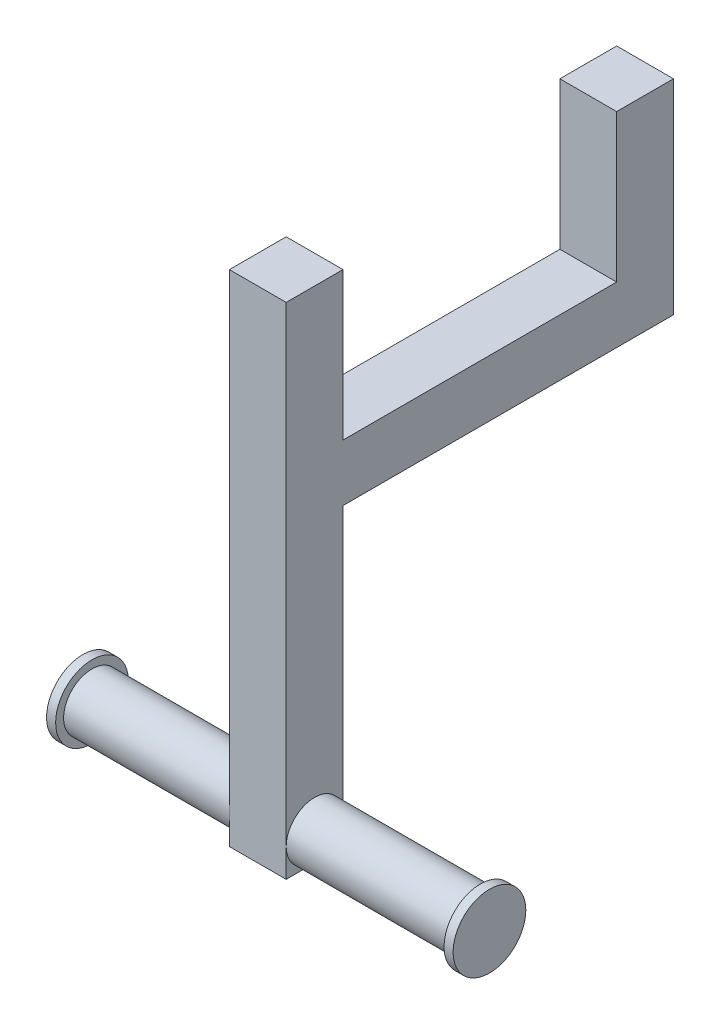
SolidWorks part; units mm, degrees
ref_plane "Front Plane" through (0, 0, 0) normal (0, 0, 1) x (1, 0, 0)
ref_plane "Top Plane" through (0, 0, 0) normal (0, 1, 0) x (1, 0, 0)
ref_plane "Right Plane" through (0, 0, 0) normal (1, 0, 0) x (0, 0, -1)
sketch "Sketch1" plane through (0, 0, 0) normal (0, 1, 0) x (1, 0, 0)
  line L0 (-60.0667, 70.9333) -> (-60.0667, -99.5667)
  line L1 (-85.0667, 70.9333) -> (-60.0667, 70.9333)
  line L2 (-85.0667, 70.9333) -> (-85.0667, -99.5667)
  line L3 (-85.0667, -99.5667) -> (-60.0667, -99.5667)
  line L5 (-85.0667, 70.9333) -> (-60.0667, 70.9333)
  line L6 (-85.0667, 70.9333) -> (-85.0667, 45.9333)
  line L7 (-85.0667, 45.9333) -> (-60.0667, 45.9333)
  line L8 (-60.0667, 70.9333) -> (-60.0667, 45.9333)
  line L9 (-85.0667, -99.5667) -> (-60.0667, -99.5667)
  line L10 (-85.0667, -99.5667) -> (-85.0667, -74.5667)
  line L11 (-85.0667, -74.5667) -> (-60.0667, -74.5667)
  line L12 (-60.0667, -99.5667) -> (-60.0667, -74.5667)
  dimension "D1" = 170.5
  dimension "D2" = 25
  dimension "D3" = 25
  dimension "D4" = 25
extrude "Boss-Extrude1" add sketch "Sketch1" along normal blind 25 contours L2 L11 L0 L7 | L2 L7 L0 L1 | L11 L2 L3 L0 region at (-72.5667, 0, -58.4333) region at (-72.5667, 0, 14.3167) region at (-72.5667, 0, 87.0667)
extrude "Boss-Extrude2" add sketch "Sketch1<8>" along normal blind 90 contours L2 L7 L0 L1 | L11 L2 L3 L0 region at (-72.5667, 0, -58.4333) region at (-72.5667, 0, 87.0667)
sketch "Sketch1<8>" plane through (0, 0, 0) normal (0, 1, 0) x (1, 0, 0) same geometry as "Sketch1"
extrude "Boss-Extrude3" add sketch "Sketch1<9>" along normal blind 90 and the other way blind 130 contours L11 L2 L3 L0 region at (-72.5667, 0, 87.0667)
sketch "Sketch1<9>" plane through (0, 0, 0) normal (0, 1, 0) x (1, 0, 0) same geometry as "Sketch1"
sketch "Sketch2" plane through (-60.0667, 0, 0) normal (1, 0, 0) x (0, 0, -1)
  line L0 (-74.5667, -130) -> (-74.5667, 0) construction
  line L1 (-99.5667, -130) -> (-74.5667, -130)
  line L2 (-99.5667, -130) -> (-99.5667, -105)
  line L3 (-99.5667, -105) -> (-74.5667, -105)
  line L4 (-74.5667, -130) -> (-74.5667, -105)
  line L5 (-99.5667, -105) -> (-74.5667, -130)
  circle A0 centre (-87.0667, -117.5) radius 12.5
  dimension "D1" = 25
extrude "Boss-Extrude4" add sketch "Sketch2" along normal blind 75 and the other way blind 100 contours A0 L5 | L5 A0 region at (-60.0667, -121.2513, 90.818) region at (-60.0667, -113.7487, 83.3153)
sketch "Sketch3" plane through (14.9333, 0, 0) normal (1, 0, 0) x (0, 0, -1)
  line L0 (-87.0667, -105) -> (-87.0667, -130)
  arc A0 (-74.5667, -117.5) -> (-99.5667, -117.5) centre (-87.0667, -117.5) ccw construction
  circle A1 centre (-87.0667, -117.5) radius 16
  circle M1 centre (-87.0667, -117.5) radius 12.5
extrude "Boss-Extrude5" add sketch "Sketch3" along normal blind 2 and the other way blind 2 contours A1 M1 | L0 M1 | L0 M1 region at (14.9333, -117.5, 81.7615) region at (14.9333, -117.5, 92.3718) region at (14.9333, -117.5, 102.6141)
sketch "Sketch4" plane through (-160.0667, 0, 0) normal (-1, 0, 0) x (0, 0, 1)
  circle A0 centre (87.0667, -117.5) radius 16
extrude "Boss-Extrude6" add sketch "Sketch4" along normal blind 2 and the other way blind 2
